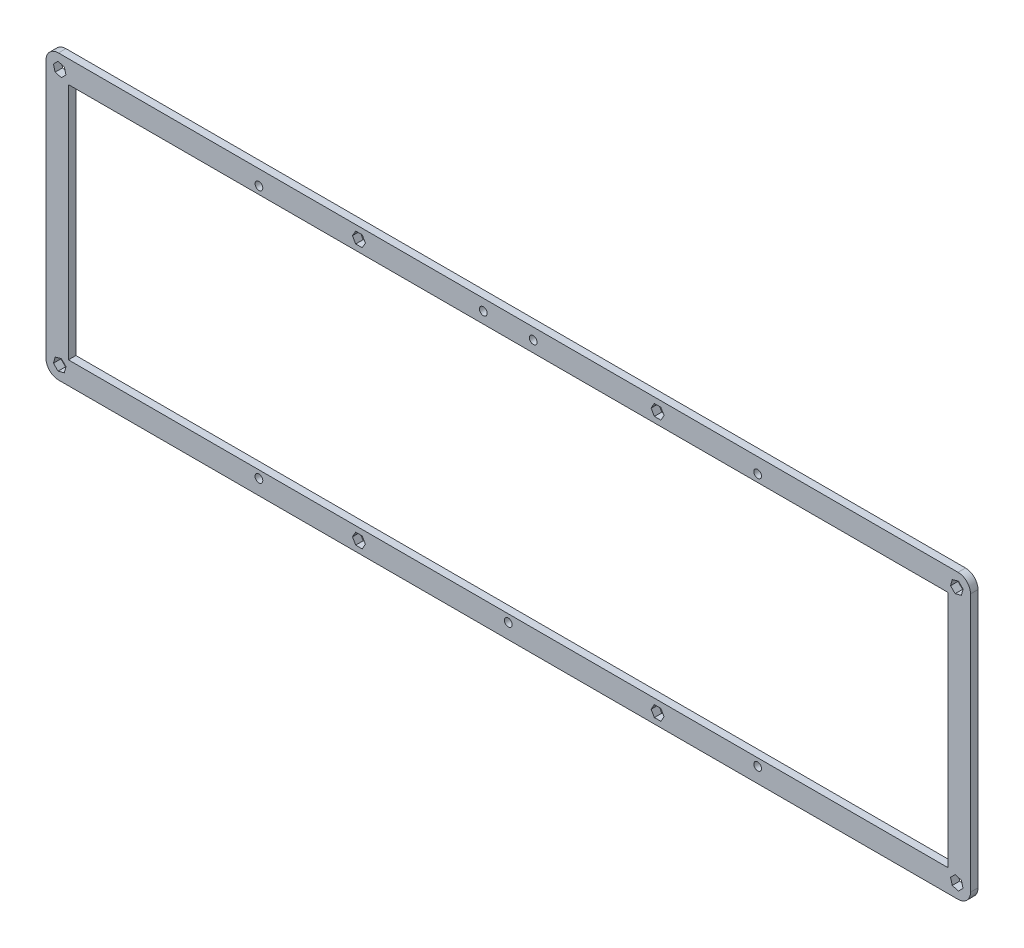
SolidWorks part; units mm, degrees
ref_plane "Front Plane" through (0, 0, 0) normal (0, 0, 1) x (1, 0, 0)
ref_plane "Top Plane" through (0, 0, 0) normal (0, 1, 0) x (1, 0, 0)
ref_plane "Right Plane" through (0, 0, 0) normal (1, 0, 0) x (0, 0, -1)
sketch "Model" plane through (0, 0, 0) normal (0, 0, 1) x (1, 0, 0)
  line L0 (0, 108.6) -> (0, 5)
  line L1 (365.775, 0) -> (5, 0)
  line L2 (370.775, 108.6) -> (370.775, 5)
  line L3 (5, 113.6) -> (365.775, 113.6)
  line L4 (9, 9) -> (361.775, 9)
  line L5 (361.775, 9) -> (361.775, 104.6)
  line L6 (9, 104.6) -> (361.775, 104.6)
  line L7 (365.9474, 110.6095) -> (367.7845, 108.7724)
  line L8 (367.7845, 108.7724) -> (367.1121, 106.2629)
  line L9 (367.1121, 106.2629) -> (364.6026, 105.5905)
  line L10 (364.6026, 105.5905) -> (362.7655, 107.4276)
  line L11 (362.7655, 107.4276) -> (363.4379, 109.9371)
  line L12 (363.4379, 109.9371) -> (365.9474, 110.6095)
  line L13 (4.8276, 110.6095) -> (2.9905, 108.7724)
  line L14 (2.9905, 108.7724) -> (3.6629, 106.2629)
  line L15 (3.6629, 106.2629) -> (6.1724, 105.5905)
  line L16 (6.1724, 105.5905) -> (8.0095, 107.4276)
  line L17 (8.0095, 107.4276) -> (7.3371, 109.9371)
  line L18 (7.3371, 109.9371) -> (4.8276, 110.6095)
  line L19 (365.9474, 2.9905) -> (367.7845, 4.8276)
  line L20 (367.7845, 4.8276) -> (367.1121, 7.3371)
  line L21 (367.1121, 7.3371) -> (364.6026, 8.0095)
  line L22 (364.6026, 8.0095) -> (362.7655, 6.1724)
  line L23 (362.7655, 6.1724) -> (363.4379, 3.6629)
  line L24 (363.4379, 3.6629) -> (365.9474, 2.9905)
  line L25 (126.799, 2.25) -> (124.201, 2.25)
  line L26 (124.201, 2.25) -> (122.9019, 4.5)
  line L27 (122.9019, 4.5) -> (124.201, 6.75)
  line L28 (124.201, 6.75) -> (126.799, 6.75)
  line L29 (126.799, 6.75) -> (128.0981, 4.5)
  line L30 (128.0981, 4.5) -> (126.799, 2.25)
  line L31 (4.8276, 2.9905) -> (2.9905, 4.8276)
  line L32 (2.9905, 4.8276) -> (3.6629, 7.3371)
  line L33 (3.6629, 7.3371) -> (6.1724, 8.0095)
  line L34 (6.1724, 8.0095) -> (8.0095, 6.1724)
  line L35 (8.0095, 6.1724) -> (7.3371, 3.6629)
  line L36 (7.3371, 3.6629) -> (4.8276, 2.9905)
  line L37 (9, 9) -> (9, 104.6)
  line L38 (126.799, 111.35) -> (124.201, 111.35)
  line L39 (124.201, 111.35) -> (122.9019, 109.1)
  line L40 (122.9019, 109.1) -> (124.201, 106.85)
  line L41 (124.201, 106.85) -> (126.799, 106.85)
  line L42 (126.799, 106.85) -> (128.0981, 109.1)
  line L43 (128.0981, 109.1) -> (126.799, 111.35)
  line L44 (243.976, 2.25) -> (246.574, 2.25)
  line L45 (246.574, 2.25) -> (247.8731, 4.5)
  line L46 (247.8731, 4.5) -> (246.574, 6.75)
  line L47 (246.574, 6.75) -> (243.976, 6.75)
  line L48 (243.976, 6.75) -> (242.6769, 4.5)
  line L49 (242.6769, 4.5) -> (243.976, 2.25)
  line L50 (243.976, 111.35) -> (246.574, 111.35)
  line L51 (246.574, 111.35) -> (247.8731, 109.1)
  line L52 (247.8731, 109.1) -> (246.574, 106.85)
  line L53 (246.574, 106.85) -> (243.976, 106.85)
  line L54 (243.976, 106.85) -> (242.6769, 109.1)
  line L55 (242.6769, 109.1) -> (243.976, 111.35)
  arc A0 (365.775, 0) -> (370.775, 5) centre (365.775, 5) ccw
  arc A1 (370.775, 108.6) -> (365.775, 113.6) centre (365.775, 108.6) ccw
  arc A2 (0, 5) -> (5, 0) centre (5, 5) ccw
  arc A3 (5, 113.6) -> (0, 108.6) centre (5, 108.6) ccw
  circle A4 centre (195.3875, 109.1) radius 1.55
  circle A5 centre (175.3875, 109.1) radius 1.55
  circle A6 centre (85.3875, 107.6) radius 1.55
  circle A7 centre (285.3875, 107.6) radius 1.55
  circle A8 centre (85.3875, 6) radius 1.55
  circle A9 centre (185.3875, 6) radius 1.55
  circle A10 centre (285.3875, 6) radius 1.55
  dimension "D2" = 3.1
  dimension "D3" = 3.1
  dimension "D4" = 3.1
  dimension "D5" = 3.1
  dimension "D6" = 3.1
  dimension "D1" = 113.6
extrude "Boss-Extrude1" add sketch "Model" along normal blind 3
